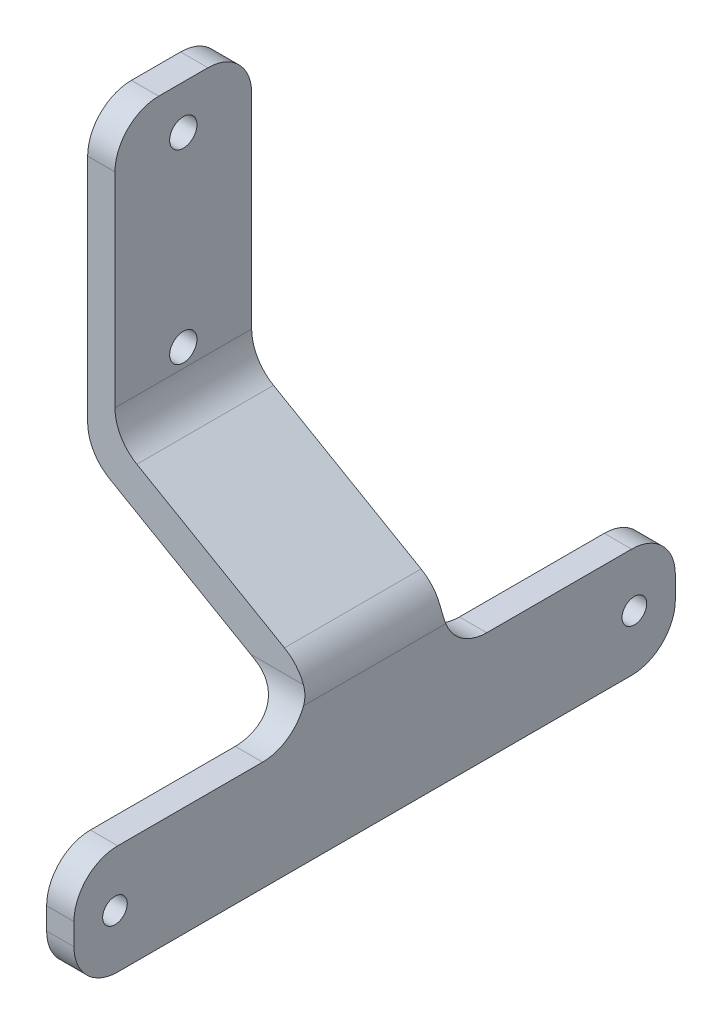
SolidWorks part; units mm, degrees
ref_plane "Front Plane" through (0, 0, 0) normal (0, 0, 1) x (1, 0, 0)
ref_plane "Top Plane" through (0, 0, 0) normal (0, 1, 0) x (1, 0, 0)
ref_plane "Right Plane" through (0, 0, 0) normal (1, 0, 0) x (0, 0, -1)
sketch "Sketch1" plane through (0, 0, 0) normal (0, 0, 1) x (1, 0, 0)
  line L0 (0, 0) -> (0, 25)
  line L1 (0, 25) -> (30, 25)
  line L2 (30, 25) -> (30, 0)
  line L3 (30, 0) -> (0, 0)
  dimension "D1" = 30
  dimension "D2" = 25
extrude "Boss-Extrude1" add sketch "Sketch1" along normal mid plane 25
sketch "Sketch2" plane through (30, 0, 0) normal (1, 0, 0) x (0, 0, -1)
  line L1 (-55, -25) -> (55, -25)
  line L2 (-55, -25) -> (-55, -5)
  line L3 (-55, -5) -> (55, -5)
  line L4 (55, -25) -> (55, -5)
  line L5 (-55, -25) -> (55, -5) construction
  line L6 (-55, -5) -> (55, -25) construction
  line L7 (12.5, 0) -> (12.5, 25) construction
  line L8 (-12.5, 25) -> (12.5, 25) construction
  line L9 (-12.5, 0) -> (12.5, 0) construction
  line L11 (-12.5, 25) -> (12.5, 25)
  line L12 (-12.5, 25) -> (-12.5, -5)
  line L13 (-12.5, -5) -> (12.5, -5)
  line L14 (12.5, 25) -> (12.5, -5)
  point P0 (0, -15)
  point P10 (0, 25)
  line M5 (12.5, 0) -> (12.5, 25)
  line M6 (12.5, 25) -> (-12.5, 25)
  line M7 (-12.5, 25) -> (-12.5, 0)
  line M8 (-12.5, 0) -> (12.5, 0)
  dimension "D1" = 110
  dimension "D2" = 20
  dimension "D3" = 5
extrude "Boss-Extrude2" add sketch "Sketch2" along normal blind 5 contours M8 M5 M6 M7 | L14 L12 L3 M8 | L1 L4 L3 L2 region at (30, -15, 0) region at (30, -2.5, 0) region at (30, 12.5, 0)
sketch "Sketch5" plane through (0, 0, 0) normal (-1, 0, 0) x (0, 0, 1)
  line L0 (12.5, 25) -> (12.5, 0) construction
  line L1 (-12.5, 0) -> (12.5, 0)
  line L2 (-12.5, 0) -> (-12.5, 75)
  line L3 (-12.5, 75) -> (12.5, 75)
  line L4 (12.5, 0) -> (12.5, 75)
  dimension "D1" = 75
extrude "Boss-Extrude4" add sketch "Sketch5" along normal blind 5 contours L2 L1 L4 L3
sketch "Sketch6" plane through (35, 0, 0) normal (1, 0, 0) x (0, 0, -1)
  line L0 (-47.5, -15) -> (47.5, -15) construction
  line L1 (-55, -25) -> (-55, -5) construction
  circle A0 centre (-47.5, -15) radius 2.25
  circle A1 centre (47.5, -15) radius 2.25
  point P4 (0, -15)
  point P8 (-55, -15)
  dimension "D1" = 4.5
  dimension "D2" = 95
extrude "Cut-Extrude1" cut sketch "Sketch6" against normal through all
sketch "Sketch7" plane through (0, 0, 0) normal (1, 0, 0) x (0, 0, -1)
  line L0 (12.5, 75) -> (-12.5, 75) construction
  line L1 (12.5, 25) -> (-12.5, 25) construction
  circle A0 centre (0, 67) radius 2.5
  circle A1 centre (0, 33) radius 2.5
  point P7 (0, 75)
  dimension "D1" = 5
  dimension "D2" = 8
  dimension "D3" = 8
extrude "Cut-Extrude2" cut sketch "Sketch7" against normal through all
chamfer "Chamfer1" distance 35 angle 30 2 edges at (-5, 0, 0) (35, 25, 0) first distance on face at (12.5, 0, 0) first distance on face at (17.5, 25, 0)
fillet "Fillet1" radius 8 10 edges at (32.5, -25, 55) (32.5, -5, 55) (32.5, -25, -55) (32.5, -5, -55) (30, 0, 0) (35, 4.7927, 0) (-5, 20.2073, 0) (0, 25, 0) (-2.5, 75, 12.5) (-2.5, 75, -12.5)
fillet "Fillet2" radius 8 2 edges at (32.5, -5, -12.5) (32.5, -5, 12.5)
